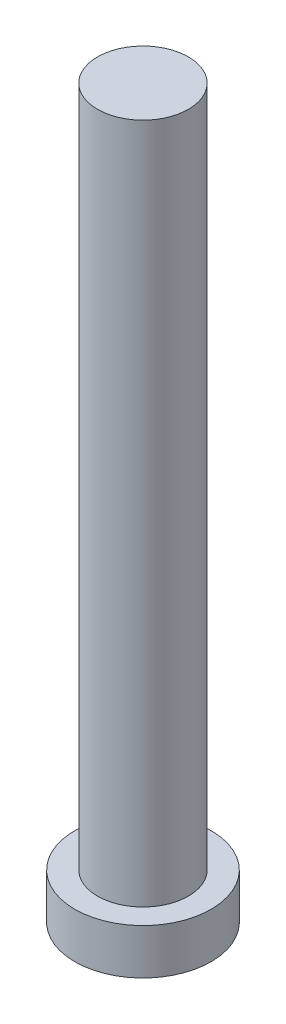
SolidWorks part; units mm, degrees
ref_plane "Front Plane" through (0, 0, 0) normal (0, 0, 1) x (1, 0, 0)
ref_plane "Top Plane" through (0, 0, 0) normal (0, 1, 0) x (1, 0, 0)
ref_plane "Right Plane" through (0, 0, 0) normal (1, 0, 0) x (0, 0, -1)
sketch "Sketch1" plane through (0, 0, 0) normal (0, 1, 0) x (1, 0, 0)
  circle A0 centre (0, 0) radius 15
  dimension "D1" = 30
extrude "Boss-Extrude1" add sketch "Sketch1" along normal blind 10
sketch "Sketch2" plane through (0, 10, 0) normal (0, 1, 0) x (1, 0, 0)
  circle A0 centre (0, 0) radius 10
  dimension "D1" = 20
extrude "Boss-Extrude2" add sketch "Sketch2" along normal blind 150
ref_axis "Axis1" through (0, 160, 0) along (0, -1, 0)
